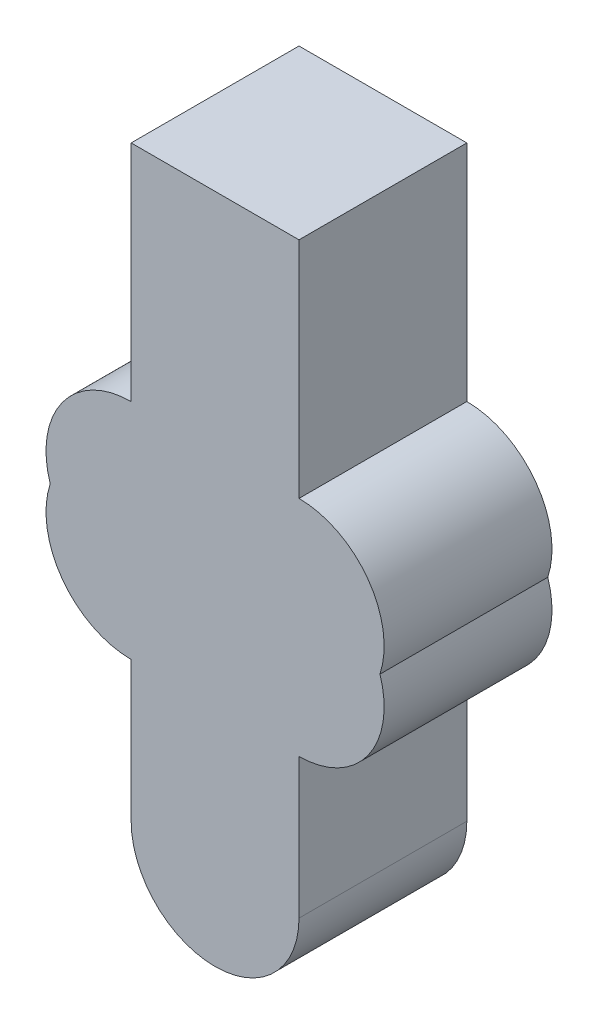
SolidWorks part; units mm, degrees
ref_plane "Спереди" through (0, 0, 0) normal (0, 0, 1) x (1, 0, 0)
ref_plane "Сверху" through (0, 0, 0) normal (0, 1, 0) x (1, 0, 0)
ref_plane "Справа" through (0, 0, 0) normal (1, 0, 0) x (0, 0, -1)
other "Configuration Table"
sketch "Канал_6" plane through (0, 0, 0) normal (0, 0, 1) x (1, 0, 0)
  line L0 (-3, -21) -> (3, -21)
  line L1 (3, -21) -> (3, 0)
  line L2 (3, 0) -> (-3, 0)
  line L3 (-3, 0) -> (-3, -21)
  line L4 (-3, -21) -> (3, 0) construction
  point P4 (0, -10.5)
  dimension "Ширина" = 6
  dimension "Глубина" = 21
  dimension "Положение_ОтКромки" = 10.5
extrude "Канал_сквозной" add sketch "Канал_6" along normal blind 6
sketch "Карман_гайки" plane through (0, 0, 0) normal (0, 0, 1) x (1, 0, 0)
  line L0 (-5.15, -15.1) -> (5.15, -15.1)
  line L1 (5.15, -15.1) -> (5.15, -8.9)
  line L2 (5.15, -8.9) -> (-5.15, -8.9)
  line L3 (-5.15, -8.9) -> (-5.15, -15.1)
  line L4 (-5.15, -15.1) -> (5.15, -8.9) construction
  point P4 (0, -12)
  dimension "Ширина" = 10.3
  dimension "Глубина" = 6.2
  dimension "Положение_ОтКромки" = 12
extrude "Гайка_10_3х6_2" add sketch "Карман_гайки" along normal blind 6
sketch "Разгрузка_угла_1" plane through (0, 0, 0) normal (0, 0, 1) x (1, 0, 0)
  circle A0 centre (-2.9933, -12.9433) radius 3.05
  dimension "Диаметр1" = 6.1
  dimension "Центр1_ПоОси" = 2.9933
  dimension "Центр1_ОтКромки" = 12.9433
extrude "Угол_фреза6_1" add sketch "Разгрузка_угла_1" along normal blind 6
sketch "Разгрузка_угла_2" plane through (0, 0, 0) normal (0, 0, 1) x (1, 0, 0)
  circle A0 centre (-2.9933, -11.0567) radius 3.05
  dimension "Диаметр1" = 6.1
  dimension "Центр1_ПоОси" = 2.9933
  dimension "Центр1_ОтКромки" = 11.0567
extrude "Угол_фреза6_2" add sketch "Разгрузка_угла_2" along normal blind 6
sketch "Разгрузка_угла_3" plane through (0, 0, 0) normal (0, 0, 1) x (1, 0, 0)
  circle A0 centre (2.9933, -12.9433) radius 3.05
  dimension "Диаметр1" = 6.1
  dimension "Центр1_ПоОси" = 2.9933
  dimension "Центр1_ОтКромки" = 12.9433
extrude "Угол_фреза6_3" add sketch "Разгрузка_угла_3" along normal blind 6
sketch "Разгрузка_угла_4" plane through (0, 0, 0) normal (0, 0, 1) x (1, 0, 0)
  circle A0 centre (2.9933, -11.0567) radius 3.05
  dimension "Диаметр1" = 6.1
  dimension "Центр1_ПоОси" = 2.9933
  dimension "Центр1_ОтКромки" = 11.0567
extrude "Угол_фреза6_4" add sketch "Разгрузка_угла_4" along normal blind 6
sketch "Конец_канала" plane through (0, 0, 0) normal (0, 0, 1) x (1, 0, 0)
  circle A0 centre (0, -21) radius 3
  dimension "Центр1_ОтКромки" = 21
extrude "Круглый_конец" add sketch "Конец_канала" along normal blind 6
equation "\"D1@Круглый_конец\" = \"Толщина тонких панелей\""
equation "\"D1@Угол_фреза6_4\" = \"Толщина тонких панелей\""
equation "\"D1@Угол_фреза6_3\" = \"Толщина тонких панелей\""
equation "\"D1@Угол_фреза6_2\" = \"Толщина тонких панелей\""
equation "\"D1@Угол_фреза6_1\" = \"Толщина тонких панелей\""
equation "\"D1@Гайка_10_3х6_2\" = \"Толщина тонких панелей\""
equation "\"D1@Канал_сквозной\" = \"Толщина тонких панелей\""
equation "\"Фанера\"=6"
equation "\"Ширина шипа\"=16"
equation "\"Межосевое шипов\"=40"
equation "\"Посадочный зазор\"=0.15"
equation "\"Основная фреза\"=6"
equation "\"Мелкая фреза\"=6"
equation "\"Запас разгрузки\"=0.05"
equation "\"Ширина образца\"=84"
equation "\"Высота образца\"=50"
equation "\"Канал М6\"=6"
equation "\"Гайка под ключ\"=10.3"
equation "\"Длина кармана гайки\"=6.2"
equation "\"Отступ гайки\"=12"
equation "\"Ширина@Канал_6\" = \"Канал М6\""
equation "\"Глубина@Канал_6\" = 21"
equation "\"Положение_ОтКромки@Канал_6\" = - (-10.5)"
equation "\"Ширина@Карман_гайки\" = \"Гайка под ключ\""
equation "\"Глубина@Карман_гайки\" = \"Длина кармана гайки\""
equation "\"Положение_ОтКромки@Карман_гайки\" = - (-\"Отступ гайки\")"
equation "\"Центр1_ПоОси@Разгрузка_угла_1\" = - ((-1)*(\"Гайка под ключ\"/2-(\"Основная фреза\"/2+\"Запас разгрузки\")/sqr(2)))"
equation "\"Центр1_ОтКромки@Разгрузка_угла_1\" = - (-\"Отступ гайки\"+(-1)*(\"Длина кармана гайки\"/2-(\"Основная фреза\"/2+\"Запас разгрузки\")/sqr(2)))"
equation "\"Диаметр1@Разгрузка_угла_1\" = \"Основная фреза\"+2*\"Запас разгрузки\""
equation "\"Центр1_ПоОси@Разгрузка_угла_2\" = - ((-1)*(\"Гайка под ключ\"/2-(\"Основная фреза\"/2+\"Запас разгрузки\")/sqr(2)))"
equation "\"Центр1_ОтКромки@Разгрузка_угла_2\" = - (-\"Отступ гайки\"+(1)*(\"Длина кармана гайки\"/2-(\"Основная фреза\"/2+\"Запас разгрузки\")/sqr(2)))"
equation "\"Диаметр1@Разгрузка_угла_2\" = \"Основная фреза\"+2*\"Запас разгрузки\""
equation "\"Центр1_ПоОси@Разгрузка_угла_3\" = ((1)*(\"Гайка под ключ\"/2-(\"Основная фреза\"/2+\"Запас разгрузки\")/sqr(2)))"
equation "\"Центр1_ОтКромки@Разгрузка_угла_3\" = - (-\"Отступ гайки\"+(-1)*(\"Длина кармана гайки\"/2-(\"Основная фреза\"/2+\"Запас разгрузки\")/sqr(2)))"
equation "\"Диаметр1@Разгрузка_угла_3\" = \"Основная фреза\"+2*\"Запас разгрузки\""
equation "\"Центр1_ПоОси@Разгрузка_угла_4\" = ((1)*(\"Гайка под ключ\"/2-(\"Основная фреза\"/2+\"Запас разгрузки\")/sqr(2)))"
equation "\"Центр1_ОтКромки@Разгрузка_угла_4\" = - (-\"Отступ гайки\"+(1)*(\"Длина кармана гайки\"/2-(\"Основная фреза\"/2+\"Запас разгрузки\")/sqr(2)))"
equation "\"Диаметр1@Разгрузка_угла_4\" = \"Основная фреза\"+2*\"Запас разгрузки\""
equation "\"Центр1_ОтКромки@Конец_канала\" = - (-21)"
equation "\"Диаметр1@Конец_канала\" = \"Канал М6\""
equation "\"Ширина груза\"= 420"
equation "\"Глубина груза\"= 490"
equation "\"Высота груза\"= 297"
equation "\"Ширина ячейки\"= \"Ширина груза\" + 10"
equation "\"Глубина ячейки\"= \"Глубина груза\" + 10"
equation "\"Высота ячейки\"= \"Высота груза\" + 10 + 13"
equation "\"Колво ячеек ширина\"= 2"
equation "\"Колво ячеек высота\"= 2"
equation "\"Толщина стенки\"= \"Толщина тонких панелей\""
equation "\"Крепление дверцы\"= 5 "
equation "\"Ширина рейки\"= \"Толщина шестерни\""
equation "\"Высота рейки\"= 20"
equation "\"Высота пола\"= 2*\"Толщина тонких панелей\""
equation "\"Колво полозьев\"= 5"
equation "\"Отступ рейки\"= 20"
equation "\"Глубина каретки\"= \"Глубина ячейки\" + 30 + \"Мотор Y высота корпуса\" + 20"
equation "\"Длинна рейки\"= (\"Ширина ячейки\"+\"Толщина вертикальных стенок\"+\"Крепление дверцы\")*\"Колво ячеек ширина\"+\"Ширина ячейки выгрузки\"*\"Колво выгрузки\"+\"Толщина вертикальных стенок\"+2*\"Отступ крепления мотора фиксации\"-\"Крепление дверцы\"*\"Колво ячеек ширина\""
equation "\"Отступ шпильки\"= 26"
equation "\"Диаметр шпильки\"= 5"
equation "\"Длинна шпильки\"= (\"Высота ячейки\"+\"Толщина горизонтальных плит\"+\"Высота пола\")*\"Колво ячеек высота\"+2*(\"Толщина горизонтальных плит\"+\"Отступ рейки\")"
equation "\"Ширина пластины\"= 50  "
equation "\"Высота зона выгрузки\"= \"Высота ячейки\" * 2 + \"Толщина стенки\" * 2"
equation "\"Колво выгрузки\"= 1"
equation "\"Ширина ячейки выгрузки\"= \"Ширина ячейки\"+\"Толщина вертикальных стенок\"+2*\"Отступ крепления мотора фиксации\""
equation "\"Отступ крепления мотора фиксации\"= (\"Ширина пластины\"+20-\"Толщина вертикальных стенок\")/2"
equation "\"Мотор X ширина корпуса\"= 42.3"
equation "\"Мотор X высота корпуса\"= 42.3"
equation "\"Мотор X длина корпуса\"= 40"
equation "\"Мотор X вылет вала\"= 19.8"
equation "\"Мотор Y ширина корпуса\"= 42.3"
equation "\"Мотор Y высота корпуса\"= 42.3"
equation "\"Мотор Y длина корпуса\"= 48"
equation "\"Мотор Y вылет вала\"= 30"
equation "\"Мотор Z ширина корпуса\"= 42"
equation "\"Мотор Z высота корпуса\"= 42"
equation "\"Мотор Z длина корпуса\"= 40"
equation "\"Мотор Z вылет вала\"= 23"
equation "\"Мотор диаметр вала ПРЕДВ\"= 5"
equation "\"Мотор шаг крепления ПРЕДВ\"= 31"
equation "\"Мотор диаметр отверстий ПРЕДВ\"= 3"
equation "\"Мотор глубина отверстий ПРЕДВ\"= 4.5"
equation "\"Мотор диаметр буртика ПРЕДВ\"= 22"
equation "\"Мотор высота буртика ПРЕДВ\"= 2"
equation "\"Мотор диаметр шкива ПРЕДВ\"= 16"
equation "\"Мотор длина шкива ПРЕДВ\"= 12"
equation "\"Мотор отступ шкива ПРЕДВ\"= 5"
equation "\"Мотор X шаг градусов\"= 1.8"
equation "\"Мотор Y шаг градусов\"= 1.8"
equation "\"Мотор Z шаг градусов\"= 1.8"
equation "\"Мотор Y диаметр ротора\"= 25.78"
equation "\"Толщина шестерни\"= 10"
equation "\"Толщина тонких панелей\"= 6"
equation "\"Толщина вертикальных стенок\"= 18"
equation "\"Толщина горизонтальных плит\"= 18"
equation "\"Базовая высота корпуса\"= (\"Высота ячейки\"+\"Толщина тонких панелей\"+\"Высота пола\")*\"Колво ячеек высота\"+6*\"Толщина тонких панелей\"+\"Мотор X ширина корпуса\"+\"Мотор Y ширина корпуса\"+75"
equation "\"Высота корпуса\"= (\"Высота ячейки\"+\"Толщина горизонтальных плит\"+\"Высота пола\")*\"Колво ячеек высота\"+2*\"Толщина горизонтальных плит\"+4*\"Толщина тонких панелей\"+\"Мотор X ширина корпуса\"+\"Мотор Y ширина корпуса\"+75"
equation "\"Смещение центра корпуса\"= (\"Высота корпуса\"-\"Базовая высота корпуса\")/2-(\"Толщина горизонтальных плит\"-\"Толщина тонких панелей\")"
equation "\"Отметка пола\"= -\"Базовая высота корпуса\"/2+\"Толщина тонких панелей\""
equation "\"Отметка потолка\"= \"Отметка пола\"+\"Высота корпуса\"-2*\"Толщина горизонтальных плит\""
equation "\"Отметка верхней полки\"= \"Отметка потолка\"-(28+\"Толщина тонких панелей\")-\"Высота ячейки\"-\"Высота пола\""
equation "\"Отметка нижней полки\"= \"Отметка верхней полки\"-\"Высота ячейки\"-\"Высота пола\"-\"Толщина горизонтальных плит\""
